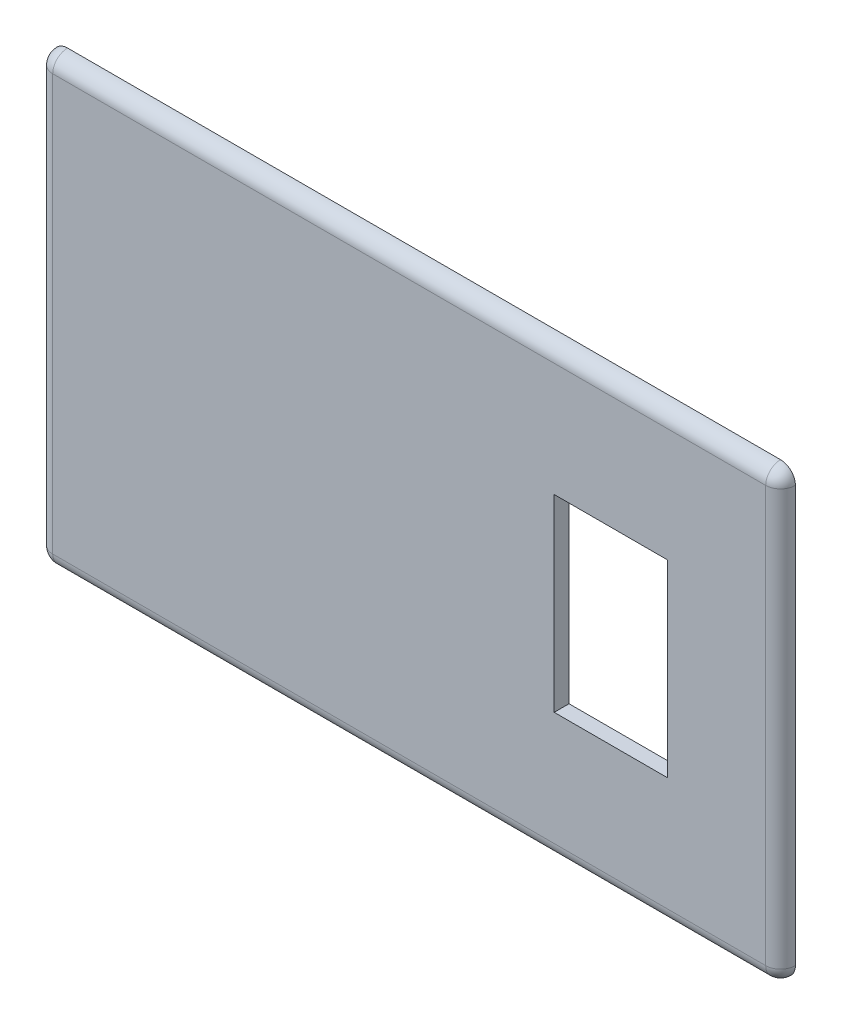
SolidWorks part; units mm, degrees
ref_plane "Front Plane" through (0, 0, 0) normal (0, 0, 1) x (1, 0, 0)
ref_plane "Top Plane" through (0, 0, 0) normal (0, 1, 0) x (1, 0, 0)
ref_plane "Right Plane" through (0, 0, 0) normal (1, 0, 0) x (0, 0, -1)
sketch "Sketch1" plane through (0, 0, 0) normal (0, 0, 1) x (1, 0, 0)
  line L1 (-50, -30) -> (50, -30)
  line L2 (-50, -30) -> (-50, 30)
  line L3 (-50, 30) -> (50, 30)
  line L4 (50, -30) -> (50, 30)
  line L5 (-50, -30) -> (50, 30) construction
  line L6 (-50, 30) -> (50, -30) construction
  point P0 (0, 0)
  dimension "D1" = 100
  dimension "D2" = 60
extrude "Boss-Extrude1" add sketch "Sketch1" along normal blind 2 contours L2 L3 L4 L1
fillet "Fillet1" radius 2 4 edges at (-50, 0, 2) (0, -30, 2) (50, 0, 2) (0, 30, 2)
sketch "Sketch2" plane through (0, 0, 2) normal (0, 0, 1) x (1, 0, 0)
  line L0 (27.14, 0) -> (0, 0) construction
  line L1 (34.76, 12.7) -> (19.52, 12.7)
  line L2 (34.76, 12.7) -> (34.76, -12.7)
  line L3 (34.76, -12.7) -> (19.52, -12.7)
  line L4 (19.52, 12.7) -> (19.52, -12.7)
  line L5 (34.76, 12.7) -> (19.52, -12.7) construction
  line L6 (34.76, -12.7) -> (19.52, 12.7) construction
  line L8 (50, -28) -> (50, 28) construction
  point P0 (27.14, 0)
  point P5 (22.2014, 0)
  point P6 (0, 0)
  point P10 (22.5684, 0)
  dimension "D1" = 25.4
  dimension "D2" = 15.24
  dimension "D3" = 15.24
extrude "Cut-Extrude1" cut sketch "Sketch2" against normal through all
